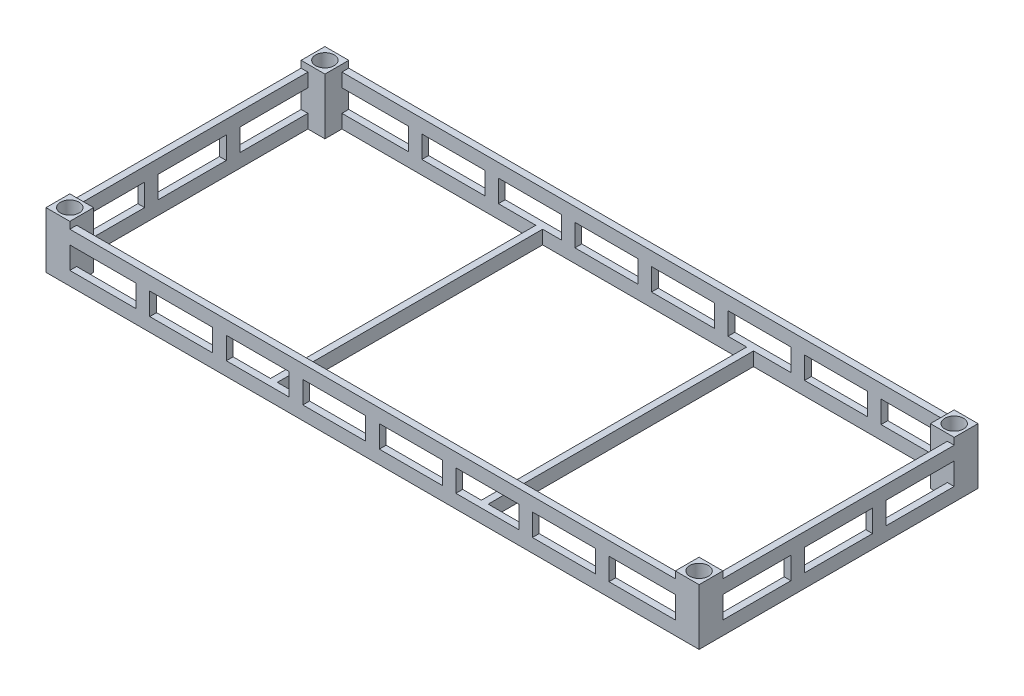
SolidWorks part; units mm, degrees
ref_plane "Front Plane" through (0, 0, 0) normal (0, 0, 1) x (1, 0, 0)
ref_plane "Top Plane" through (0, 0, 0) normal (0, 1, 0) x (1, 0, 0)
ref_plane "Right Plane" through (0, 0, 0) normal (1, 0, 0) x (0, 0, -1)
sketch "Sketch1" plane through (0, 0, 0) normal (0, 1, 0) x (1, 0, 0)
  line L0 (0, 820) -> (60, 820)
  line L1 (0, 0) -> (1920, 0)
  line L2 (0, 0) -> (0, 820)
  line L3 (0, 820) -> (1920, 820)
  line L4 (1920, 0) -> (1920, 820)
  line L5 (60, 820) -> (60, 760)
  line L6 (60, 760) -> (0, 760)
  line L7 (0, 760) -> (0, 765)
  line L8 (0, 765) -> (60, 765)
  line L9 (60, 765) -> (55, 765)
  line L10 (55, 765) -> (55, 820)
  line L11 (55, 820) -> (55, 815)
  line L12 (55, 815) -> (0, 815)
  line L13 (0, 815) -> (5, 815)
  line L14 (5, 815) -> (5, 765)
  line L15 (0, 760) -> (60, 820)
  line L16 (960, 0) -> (960, 820)
  line L17 (960, 820) -> (960, 0)
  line L18 (960, 410) -> (0, 410)
  line L19 (1920, 760) -> (1860, 820)
  line L20 (1915, 815) -> (1915, 765)
  line L21 (1920, 815) -> (1915, 815)
  line L22 (1865, 815) -> (1920, 815)
  line L23 (1865, 820) -> (1865, 815)
  line L24 (1865, 765) -> (1865, 820)
  line L25 (1860, 765) -> (1865, 765)
  line L26 (1920, 765) -> (1860, 765)
  line L27 (1920, 760) -> (1920, 765)
  line L28 (1860, 760) -> (1920, 760)
  line L29 (1860, 820) -> (1860, 760)
  line L30 (1920, 820) -> (1860, 820)
  line L31 (1920, 0) -> (1860, 0)
  line L32 (1860, 0) -> (1860, 60)
  line L33 (1860, 60) -> (1920, 60)
  line L34 (1920, 60) -> (1920, 55)
  line L35 (1920, 55) -> (1860, 55)
  line L36 (1860, 55) -> (1865, 55)
  line L37 (1865, 55) -> (1865, 0)
  line L38 (1865, 0) -> (1865, 5)
  line L39 (1865, 5) -> (1920, 5)
  line L40 (1920, 5) -> (1915, 5)
  line L41 (1915, 5) -> (1915, 55)
  line L42 (1920, 60) -> (1860, 0)
  line L43 (0, 60) -> (60, 0)
  line L44 (5, 5) -> (5, 55)
  line L45 (0, 5) -> (5, 5)
  line L46 (55, 5) -> (0, 5)
  line L47 (55, 0) -> (55, 5)
  line L48 (55, 55) -> (55, 0)
  line L49 (60, 55) -> (55, 55)
  line L50 (0, 55) -> (60, 55)
  line L51 (0, 60) -> (0, 55)
  line L52 (60, 60) -> (0, 60)
  line L53 (60, 0) -> (60, 60)
  line L54 (0, 0) -> (1920, 0)
  line L55 (0, 0) -> (60, 0)
  line L56 (60, 0) -> (60, 20)
  line L57 (60, 20) -> (1860, 20)
  line L58 (1920, 60) -> (1900, 60)
  line L59 (1900, 60) -> (1900, 760)
  line L60 (60, 800) -> (1860, 800)
  line L61 (20, 60) -> (20, 760)
  circle A0 centre (30, 790) radius 25
  circle A1 centre (1890, 790) radius 25
  circle A2 centre (1890, 30) radius 25
  circle A3 centre (30, 30) radius 25
extrude "Boss-Extrude1" add sketch "Sketch1" along normal blind 165 contours L14 L12 L2 L8 | A0 L14 L15 | A0 L15 L8 | L2 L15 L8 | L15 L6 L5 L8 | A0 L8 L10 | L15 L10 L8 L5 | A0 L12 L14 | L12 L10 L0 L2 | A0 L15 L12 | A0 L10 L15 | L10 L15 L3 | L5 L60 L16 L3 | L18 L61 L6 L2 | L52 L61 L18 L2 | L2 L50 L43 | L50 L2 L45 L44 | L49 L53 L52 L43 L50 | L43 A3 L50 | L44 A3 L43 | L50 A3 L48 | L43 L53 L49 L48 | L43 A3 L46 | L48 A3 L43 | L1 L47 L46 L45 L2 | L47 L1 L43 | L46 A3 L44 | L57 L53 L1 L16 | L57 L16 L1 L32 | L42 L37 L35 L32 | A2 L37 L42 | A2 L42 L39 | L37 L42 L1 | L39 L37 L31 L4 | A2 L39 L41 | L41 L39 L4 L35 | L42 L33 L32 L35 | A2 L35 L37 | A2 L42 L35 | L4 L42 L35 | A2 L41 L42 | L59 L33 L4 L28 | L25 L29 L28 L19 L26 | L4 L26 L19 | L20 A1 L19 | L19 A1 L26 | L26 L4 L21 L20 | L3 L23 L22 L21 L4 | L22 A1 L20 | L23 L3 L19 | L19 L29 L25 L24 | L24 A1 L19 | L19 A1 L22 | L26 A1 L24 | L16 L60 L29 L3 region at (27.5, 0, -817.5) region at (56.6667, 0, -818.3333) region at (2.5, 0, -790) region at (510, 0, -810) region at (57.5397, 0, -791.2698) region at (46.0846, 0, -812.747) region at (52.747, 0, -806.0846) region at (1.6667, 0, -763.3333) region at (10.5842, 0, -809.4158) region at (1410, 0, -810) region at (49.4158, 0, -770.5842) region at (10, 0, -585) region at (31.2319, 0, -762.4638) region at (13.9154, 0, -767.253) region at (7.253, 0, -773.9154) region at (1863.3333, 0, -818.3333) region at (1862.4603, 0, -791.2698) region at (10, 0, -235) region at (1892.5, 0, -817.5) region at (1873.9154, 0, -812.747) region at (1867.253, 0, -806.0846) region at (1.6667, 0, -56.6667) region at (31.2319, 0, -57.5362) region at (1909.4158, 0, -809.4158) region at (1870.5842, 0, -770.5842) region at (1888.7681, 0, -762.4638) region at (1410, 0, -10) region at (510, 0, -10) region at (2.5, 0, -30) region at (13.9154, 0, -52.747) region at (7.253, 0, -46.0846) region at (1917.5, 0, -790) region at (1912.747, 0, -773.9154) region at (1906.0846, 0, -767.253) region at (57.5397, 0, -28.7302) region at (1862.4603, 0, -28.7302) region at (27.5, 0, -2.5) region at (10.5842, 0, -10.5842) region at (49.4158, 0, -49.4158) region at (1918.3333, 0, -763.3333) region at (1910, 0, -410) region at (56.6667, 0, -1.6667) region at (1863.3333, 0, -1.6667) region at (1888.7681, 0, -57.5362) region at (52.747, 0, -13.9154) region at (46.0846, 0, -7.253) region at (1892.5, 0, -2.5) region at (1873.9154, 0, -7.253) region at (1867.253, 0, -13.9154) region at (1870.5842, 0, -49.4158) region at (1918.3333, 0, -56.6667) region at (1909.4158, 0, -10.5842) region at (1906.0846, 0, -52.747) region at (1917.5, 0, -30) region at (1912.747, 0, -46.0846)
sketch "Sketch2" plane through (0, 0, 0) normal (0, 0, 1) x (1, 0, 0)
  line L0 (0, 165) -> (60, 165)
  line L1 (0, 165) -> (1920, 165) construction
  line L2 (60, 165) -> (60, 145)
  line L3 (60, 145) -> (1860, 145)
  line L4 (1860, 145) -> (1860, 165)
  line L5 (1860, 165) -> (60, 165)
  line L6 (1860, 145) -> (1860, 105)
  line L7 (1860, 105) -> (60, 105)
  line L8 (60, 105) -> (60, 145)
  line L9 (60, 105) -> (60, 40)
  line L10 (60, 40) -> (1860, 40)
  line L11 (1860, 105) -> (1860, 40)
  line L12 (960, 105) -> (960, 40)
  line L13 (960, 40) -> (980, 40)
  line L14 (980, 40) -> (980, 105)
  line L15 (980, 105) -> (940, 105)
  line L16 (940, 105) -> (940, 40)
  line L17 (960, 105) -> (1860, 105)
  line L18 (1860, 105) -> (1410, 105)
  line L19 (960, 105) -> (1410, 105)
  line L20 (1185, 105) -> (1185, 40)
  line L21 (1185, 40) -> (1410, 40)
  line L22 (1410, 40) -> (1410, 105)
  line L23 (1635, 105) -> (1635, 40)
  line L24 (960, 105) -> (735, 105)
  line L25 (735, 105) -> (735, 40)
  line L26 (735, 40) -> (510, 40)
  line L27 (510, 40) -> (510, 105)
  line L28 (510, 105) -> (285, 105)
  line L29 (285, 105) -> (285, 40)
  line L30 (755, 40) -> (755, 105)
  line L31 (755, 105) -> (715, 105)
  line L32 (735, 40) -> (755, 40)
  line L33 (715, 105) -> (715, 40)
  line L34 (735, 105) -> (735, 40)
  line L35 (530, 40) -> (530, 105)
  line L36 (530, 105) -> (490, 105)
  line L37 (510, 40) -> (530, 40)
  line L38 (490, 105) -> (490, 40)
  line L39 (510, 105) -> (510, 40)
  line L40 (305, 40) -> (305, 105)
  line L41 (305, 105) -> (265, 105)
  line L42 (285, 40) -> (305, 40)
  line L43 (265, 105) -> (265, 40)
  line L44 (285, 105) -> (285, 40)
  line L45 (1205, 40) -> (1205, 105)
  line L46 (1205, 105) -> (1165, 105)
  line L47 (1185, 40) -> (1205, 40)
  line L48 (1165, 105) -> (1165, 40)
  line L49 (1185, 105) -> (1185, 40)
  line L50 (1430, 40) -> (1430, 105)
  line L51 (1430, 105) -> (1390, 105)
  line L52 (1410, 40) -> (1430, 40)
  line L53 (1390, 105) -> (1390, 40)
  line L54 (1410, 105) -> (1410, 40)
  line L55 (1655, 40) -> (1655, 105)
  line L56 (1655, 105) -> (1615, 105)
  line L57 (1635, 40) -> (1655, 40)
  line L58 (1615, 105) -> (1615, 40)
  line L59 (1635, 105) -> (1635, 40)
  line M7 (1920, 165) -> (0, 165)
extrude "Cut-Extrude1" cut sketch "Sketch2" against normal through all both and the other way through all contours L43 L7 L9 L10 | L40 L10 L38 L28 | L35 L26 L33 L7 | L30 L10 L16 L7 | L48 L17 L14 L10 | L53 L19 L45 L21 | L58 L7 L50 L10 | L55 L10 L11 L7 | L3 L4 L2 M7 region at (960, 155, 0) region at (162.5, 72.5, 0) region at (1757.5, 72.5, 0) region at (397.5, 72.5, 0) region at (1522.5, 72.5, 0) region at (622.5, 72.5, 0) region at (1297.5, 72.5, 0) region at (847.5, 72.5, 0) region at (1072.5, 72.5, 0)
sketch "Sketch3" plane through (1920, 0, 0) normal (1, 0, 0) x (0, 0, -1)
  line L0 (820, 165) -> (760, 165)
  line L1 (0, 165) -> (820, 165) construction
  line L2 (760, 165) -> (760, 0)
  line L3 (760, 0) -> (60, 0)
  line L4 (0, 0) -> (820, 0) construction
  line L5 (60, 0) -> (60, 165)
  line L6 (60, 165) -> (760, 165)
  line L7 (60, 165) -> (60, 145)
  line L8 (60, 145) -> (760, 145)
  line L9 (410, 145) -> (310, 145)
  line L10 (310, 145) -> (310, 0)
  line L11 (310, 0) -> (270, 0)
  line L12 (270, 0) -> (270, 145)
  line L13 (410, 145) -> (410, 212.6198)
  line L14 (510, 145) -> (510, 0)
  line L15 (550, 0) -> (550, 145)
  line L16 (760, 145) -> (760, 105)
  line L17 (760, 105) -> (60, 105)
  line L18 (60, 105) -> (60, 40)
  line L19 (60, 40) -> (760, 40)
  line M9 (820, 165) -> (0, 165)
extrude "Cut-Extrude2" cut sketch "Sketch3" against normal through all both and the other way through all contours L8 L13 L6 L5 | L13 L8 L2 M9 | L10 L19 L14 L17 | L15 L19 L2 L17 | L5 L19 L12 L17 region at (1920, 155, -585) region at (1920, 155, -235) region at (1920, 72.5, -655) region at (1920, 72.5, -410) region at (1920, 72.5, -165)
sketch "Sketch5" plane through (0, 0, 0) normal (0, -1, 0) x (1, 0, 0)
  line L0 (960, 0) -> (1260, 0)
  line L1 (0, 0) -> (1920, 0) construction
  line L2 (1260, 0) -> (1260, -820)
  line L3 (0, -820) -> (1920, -820) construction
  line L4 (1260, -820) -> (1280, -820)
  line L5 (1280, -820) -> (1280, 0)
  line L6 (1280, 0) -> (1260, 0)
  line L7 (960, 0) -> (660, 0)
  line L8 (660, 0) -> (660, -820)
  line L9 (660, -820) -> (640, -820)
  line L10 (640, -820) -> (640, 0)
  line L11 (640, 0) -> (660, 0)
  line M11 (1860, -800) -> (60, -800)
  line M17 (60, -20) -> (1860, -20)
extrude "Boss-Extrude3" add sketch "Sketch5" against normal blind 40 contours L10 L8 M11 M17 | L5 L2 M11 M17 region at (1270, 0, -410) region at (650, 0, -410)
scale "Scale2" scale about centroid uniform scaling yes scale factor 0.1
sketch "Sketch6" plane through (0, 77.378, 0) normal (0, 1, 0) x (1, 0, 0)
  line L1 (1056, 369) -> (1049, 369)
  line L2 (1056, 369) -> (1056, 376)
  line L3 (1056, 376) -> (1049, 376)
  line L4 (1049, 369) -> (1049, 376)
  line L5 (864, 369) -> (871, 369)
  line L6 (864, 369) -> (864, 376)
  line L7 (864, 376) -> (871, 376)
  line L8 (871, 369) -> (871, 376)
  line L9 (1056, 451) -> (1049, 451)
  line L10 (1056, 451) -> (1056, 444)
  line L11 (1056, 444) -> (1049, 444)
  line L12 (1049, 451) -> (1049, 444)
  line L13 (864, 451) -> (871, 451)
  line L14 (864, 451) -> (864, 444)
  line L15 (864, 444) -> (871, 444)
  line L16 (871, 451) -> (871, 444)
extrude "Boss-Extrude4" add sketch "Sketch6" against normal up to surface (16.5 mm away) up to face at (867, 77.378, -369.5)
sketch "Sketch7" plane through (0, 77.378, 0) normal (0, 1, 0) x (1, 0, 0)
  line L0 (1052.5, 369) -> (1052.5, 376)
  line L1 (1049, 369) -> (1056, 369) construction
  line L2 (1056, 376) -> (1049, 376) construction
  line L3 (1056, 369) -> (864, 369)
  line L4 (864, 369) -> (864.0294, 369.2165)
  line L5 (864, 451) -> (864, 369)
  line L6 (960, 369) -> (960, 410)
  line L7 (960, 410) -> (864, 410)
  line L8 (864, 451) -> (864.0294, 450.7835)
  line L9 (1056, 451) -> (864, 451)
  line L10 (1052.5, 451) -> (1052.5, 444)
  circle A0 centre (1052.5, 372.5) radius 2.75
  circle A1 centre (867.5, 372.5) radius 2.75
  circle A2 centre (867.5, 447.5) radius 2.75
  circle A3 centre (1052.5, 447.5) radius 2.75
extrude "Cut-Extrude3" cut sketch "Sketch7" against normal through all both and the other way through all contours L0 A0 | L0 A0 | A3 L10 | A3 L10 | A2 | A1 region at (1051.3329, 77.378, -372.5) region at (1053.6671, 77.378, -372.5) region at (1053.6671, 77.378, -447.5) region at (1051.3329, 77.378, -447.5) region at (867.5, 77.378, -372.5) region at (867.5, 77.378, -447.5)
